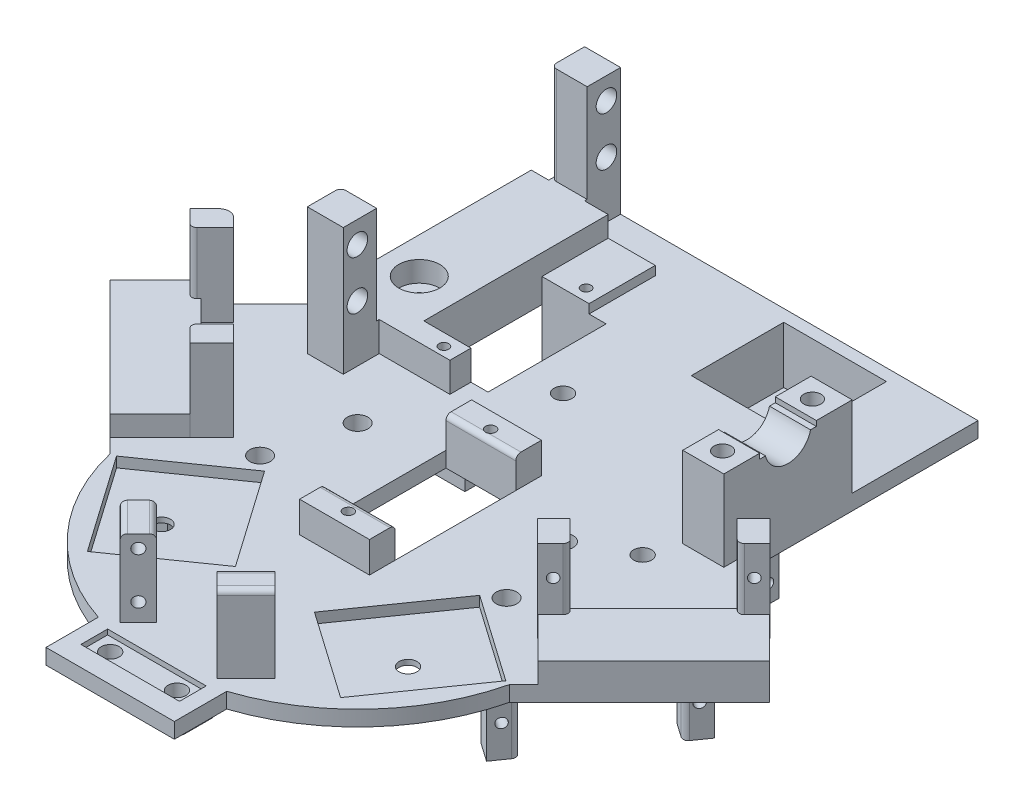
SolidWorks part; units mm, degrees
ref_plane "前视基准面" through (0, 0, 0) normal (0, 0, 1) x (1, 0, 0)
ref_plane "上视基准面" through (0, 0, 0) normal (0, 1, 0) x (1, 0, 0)
ref_plane "右视基准面" through (0, 0, 0) normal (1, 0, 0) x (0, 0, -1)
other "Configuration Table"
sketch "草图1" plane through (0, 0, 0) normal (0, 1, 0) x (1, 0, 0)
  circle A1 centre (0, 0) radius 40
  dimension "D1" = 80
extrude "凸台-拉伸1" add sketch "草图1" along normal blind 3
sketch "草图2" plane through (0, 0, 0) normal (0, -1, 0) x (-1, 0, 0)
  line L0 (-64.2199, 16.0008) -> (-38.899, -9.3201)
  line L1 (64.2199, 16.0008) -> (38.899, -9.3201)
  line L2 (-38.899, -9.3201) -> (38.899, -9.3201)
  line L3 (-64.2199, 16.0008) -> (-40, 40.2207)
  line L6 (-40, 40.2207) -> (-40, 93.8121)
  line L7 (-40, 93.8121) -> (40, 93.8121)
  line L8 (40, 93.8121) -> (40, 40.2207)
  line L9 (64.2199, 16.0008) -> (40, 40.2207)
  dimension "D1" = 77.7981
  dimension "D2" = 80
  dimension "D3" = 53.5914
  dimension "D4" = 34.2521
  dimension "D5" = 35.8091
  dimension "D6" = 53.5914
  dimension "D7" = 34.2521
  dimension "D8" = 35.8091
  dimension "D9" = 9.3201
  dimension "D10" = 56.7246
extrude "凸台-拉伸2" add sketch "草图2" against normal blind 3
sketch "草图3" plane through (0, 3, 0) normal (0, 1, 0) x (1, 0, 0)
  line L0 (-12.5, -48.1879) -> (12.5, -48.1879)
  line L1 (12.5, -48.1879) -> (12.5, -37.9967)
  line L2 (12.5, -37.9967) -> (-12.5, -37.9967)
  line L3 (-12.5, -37.9967) -> (-12.5, -48.1879)
  dimension "D1" = 37.9967
  dimension "D2" = 10.1912
  dimension "D3" = 12.5
  dimension "D4" = 12.5
extrude "凸台-拉伸3" add sketch "草图3" against normal blind 3
sketch "草图6" plane through (0, 3, 0) normal (0, 1, 0) x (1, 0, 0)
  line L3 (0, 0) -> (31.2783, -18.5118) construction
  line L5 (20.9467, 2.8224) -> (37.9031, -9.0506)
  line L6 (0, 0) -> (37.9031, -9.0506) construction
  line L7 (0, 0) -> (0, -48.1879) construction
  line L8 (37.9031, -9.0506) -> (24.6535, -27.973)
  line L9 (24.6535, -27.973) -> (7.697, -16.1)
  line L10 (7.697, -16.1) -> (20.9467, 2.8224)
  line L11 (-12.5, -48.1879) -> (12.5, -48.1879) construction
  dimension "D1" = 15.5396
  dimension "D2" = 20.7
  dimension "D3" = 23.1
  dimension "D4" = 8.7735
  dimension "D5" = 76.57
extrude "切除-拉伸2" cut sketch "草图6" against normal blind 2
mirror "镜向3" about plane through (0, 0, 0) normal (1, 0, 0) of "切除-拉伸2"
sketch "草图7" plane through (0, 1, 0) normal (0, 1, 0) x (1, 0, 0)
  circle A0 centre (-24, -14.1879) radius 1.75
  circle A1 centre (24, -14.1879) radius 1.75
  dimension "D1" = 24
  dimension "D2" = 3.5
  dimension "D4" = 3.5
  dimension "D3" = 24
  dimension "D5" = 14.1879
  dimension "D6" = 14.1879
extrude "切除-拉伸3" cut sketch "草图7" against normal blind 2
sketch "草图8" plane through (0, 3, 0) normal (0, 1, 0) x (1, 0, 0)
  line L0 (-9.6, -39.0879) -> (9.6, -39.0879)
  line L1 (9.6, -39.0879) -> (9.6, -44.2879)
  line L2 (9.6, -44.2879) -> (-9.6, -44.2879)
  line L3 (-9.6, -44.2879) -> (-9.6, -39.0879)
  dimension "D1" = 39.0879
  dimension "D2" = 5.2
  dimension "D3" = 9.6
  dimension "D4" = 9.6
extrude "切除-拉伸4" cut sketch "草图8" against normal blind 1
sketch "草图9" plane through (0, 2, 0) normal (0, 1, 0) x (1, 0, 0)
  circle A0 centre (-6.5, -41.6879) radius 1.75
  circle A1 centre (6.5, -41.6879) radius 1.75
  dimension "D1" = 3.5
  dimension "D2" = 3.5
  dimension "D3" = 6.5
  dimension "D4" = 6.5
  dimension "D5" = 41.6879
  dimension "D6" = 41.6879
extrude "切除-拉伸5" cut sketch "草图9" against normal blind 11
sketch "草图10" plane through (0, 3, 0) normal (0, 1, 0) x (1, 0, 0)
  line L13 (-14.3884, -30.4342) -> (-12.2671, -28.3129)
  line L15 (-8.7316, -36.0911) -> (-6.6103, -33.9698)
  line L18 (12.2671, -28.3129) -> (14.3884, -30.4342)
  line L21 (8.7316, -36.0911) -> (6.6103, -33.9698)
  line L22 (-6.6103, -33.9698) -> (-5.9032, -33.2627)
  line L23 (-12.2671, -28.3129) -> (-11.56, -27.6058)
  line L24 (-11.56, -27.6058) -> (-5.9032, -33.2627)
  line L25 (-8.7316, -36.0911) -> (-9.4387, -36.7982)
  line L26 (-9.4387, -36.7982) -> (-15.0955, -31.1414)
  line L27 (-15.0955, -31.1414) -> (-14.3884, -30.4342)
  line L28 (6.6103, -33.9698) -> (5.9032, -33.2627)
  line L29 (5.9032, -33.2627) -> (11.56, -27.6058)
  line L30 (11.56, -27.6058) -> (12.2671, -28.3129)
  line L31 (14.3884, -30.4342) -> (15.0955, -31.1414)
  line L32 (15.0955, -31.1414) -> (9.4387, -36.7982)
  line L33 (9.4387, -36.7982) -> (8.7316, -36.0911)
  dimension "D1" = 1
  dimension "D2" = 1
  dimension "D3" = 8
  dimension "D6" = 3
  dimension "D7" = 1
  dimension "D8" = 1
  dimension "D9" = 1
extrude "凸台-拉伸5" add sketch "草图10" along normal blind 15
fillet "圆角1" radius 1 4 edges at (8.7316, 18, 30.4342) (12.2671, 18, 33.9698) (-8.7316, 18, 30.4342) (-12.2671, 18, 33.9698)
sketch "草图12" plane through (8.0229, 0, 8.0229) normal (0.7071, 0, 0.7071) x (0.7071, 0, -0.7071)
  line L0 (-31.6944, 3) -> (-31.6944, 6.5) construction
  line L2 (-31.6944, 6.5) -> (-30.1944, 6.5) construction
  line L3 (-30.1944, 6.5) -> (-30.1944, 15.5) construction
  circle A0 centre (-30.1944, 15.5) radius 1.05
  circle A1 centre (-30.1944, 6.5) radius 1.05
  dimension "D4" = 2.1
  dimension "D5" = 2.1
  dimension "D1" = 3.5
  dimension "D2" = 1.5
  dimension "D3" = 9
extrude "切除-拉伸6" cut sketch "草图12" along normal blind 14
mirror "镜向1" about plane through (0, 0, 0) normal (1, 0, 0) of "切除-拉伸6"
sketch "草图13" plane through (0, 3, 0) normal (0, 1, 0) x (1, 0, 0)
  line L0 (32, 56.3121) -> (40, 56.3121)
  line L3 (40, 56.3121) -> (40, 31.3121)
  line L4 (40, 31.3121) -> (32, 31.3121)
  line L5 (32, 31.3121) -> (32, 56.3121)
  dimension "D1" = 25
  dimension "D2" = 8
  dimension "D3" = 32
  dimension "D4" = 56.3121
extrude "凸台-拉伸6" add sketch "草图13" along normal blind 15.75 contours L0 L3 L4 L5
sketch "草图14" plane through (40, 0, 0) normal (1, 0, 0) x (0, 0, -1)
  line L0 (56.3121, 18.75) -> (31.3121, 18.75) construction
  circle A0 centre (43.8121, 18.75) radius 4.5
  dimension "D1" = 9
extrude "切除-拉伸7" cut sketch "草图14" against normal blind 15.75
sketch "草图15" plane through (40, 0, 0) normal (1, 0, 0) x (0, 0, -1)
  line L1 (38.2871, 19.75) -> (49.3371, 19.75)
  line L2 (38.2871, 19.75) -> (38.2871, 17.75)
  line L3 (38.2871, 17.75) -> (49.3371, 17.75)
  line L4 (49.3371, 19.75) -> (49.3371, 17.75)
  line L5 (38.2871, 19.75) -> (49.3371, 17.75) construction
  line L6 (38.2871, 17.75) -> (49.3371, 19.75) construction
  point P0 (43.8121, 18.75)
  dimension "D1" = 2
  dimension "D2" = 11.05
extrude "切除-拉伸8" cut sketch "草图15" against normal blind 15.75
sketch "草图16" plane through (0, 18.75, 0) normal (0, 1, 0) x (1, 0, 0)
  circle A0 centre (36, 35.0621) radius 1.675
  circle A1 centre (36, 52.5621) radius 1.675
  dimension "D1" = 3.35
  dimension "D2" = 3.35
  dimension "D3" = 17.5
  dimension "D4" = 35.0621
  dimension "D5" = 36
  dimension "D6" = 36
extrude "切除-拉伸9" cut sketch "草图16" against normal blind 55.75
sketch "草图17" plane through (0, 3, 0) normal (0, 1, 0) x (1, 0, 0)
  line L0 (-15.8477, 73.8121) -> (-40, 73.8121)
  line L3 (-40, 73.8121) -> (-40, 33.8121)
  line L5 (-40, 33.8121) -> (-15.8477, 33.8121)
  line L6 (-15.8477, 33.8121) -> (-15.8477, 73.8121)
  dimension "D1" = 24.1523
  dimension "D2" = 33.8121
  dimension "D3" = 40
  dimension "D4" = 40
extrude "凸台-拉伸7" add sketch "草图17" along normal blind 6.75
sketch "草图18" plane through (0, 3, 0) normal (0, 1, 0) x (1, 0, 0)
  line L0 (-36.61, 73.8121) -> (-36.61, 80.8121)
  line L3 (-36.61, 80.8121) -> (-29.61, 80.8121)
  line L4 (-29.61, 80.8121) -> (-29.61, 73.8121)
  line L5 (-29.61, 73.8121) -> (-36.61, 73.8121)
  line L6 (-36.61, 33.8121) -> (-36.61, 26.8121)
  line L8 (-36.61, 26.8121) -> (-29.61, 26.8121)
  line L9 (-29.61, 26.8121) -> (-29.61, 33.8121)
  line L10 (-29.61, 33.8121) -> (-36.61, 33.8121)
  dimension "D1" = 7
  dimension "D2" = 7
  dimension "D3" = 7
  dimension "D4" = 7
  dimension "D5" = 36.61
  dimension "D6" = 33.8121
  dimension "D7" = 73.8121
  dimension "D8" = 29.61
extrude "凸台-拉伸8" add sketch "草图18" along normal blind 24.75
sketch "草图19" plane through (-36.61, 0, 0) normal (-1, 0, 0) x (0, 0, 1)
  circle A0 centre (-29.5621, 23.5) radius 2
  circle A1 centre (-29.5621, 14) radius 2
  circle A2 centre (-78.0621, 23.5) radius 2
  circle A3 centre (-78.0621, 14) radius 2
  dimension "D1" = 4
  dimension "D2" = 4
  dimension "D3" = 4
  dimension "D4" = 4
  dimension "D5" = 29.5621
  dimension "D6" = 14
  dimension "D7" = 48.5
  dimension "D8" = 48.5
  dimension "D9" = 9.5
extrude "切除-拉伸10" cut sketch "草图19" against normal blind 24.75
sketch "草图20" plane through (0, 27.75, 0) normal (0, 1, 0) x (1, 0, 0)
  line L0 (-36.61, 73.8121) -> (-29.61, 73.8121)
  line L1 (-29.61, 73.8121) -> (-29.61, 74.3121)
  line L2 (-29.61, 74.3121) -> (-36.61, 74.3121)
  line L3 (-36.61, 80.8121) -> (-36.61, 73.8121) construction
  line L4 (-36.61, 74.3121) -> (-36.61, 73.8121)
  line L5 (-29.61, 33.8121) -> (-29.61, 33.3121)
  line L6 (-29.61, 26.8121) -> (-29.61, 33.8121) construction
  line L7 (-29.61, 33.3121) -> (-36.61, 33.3121)
  line L8 (-36.61, 33.8121) -> (-36.61, 26.8121) construction
  line L9 (-36.61, 33.3121) -> (-36.61, 33.8121)
  line L10 (-36.61, 33.8121) -> (-29.61, 33.8121)
  dimension "D1" = 0.5
  dimension "D2" = 0.5
extrude "切除-拉伸11" cut sketch "草图20" against normal blind 19
fillet "圆角2" radius 1 2 edges at (-36.61, 18.25, -33.3121) (-36.61, 18.25, -74.3121)
sketch "草图21" plane through (0, 0, 0) normal (0, -1, 0) x (1, 0, 0)
  line L0 (-34.2042, 9.1029) -> (-30.518, 6.5218)
  line L1 (-30.518, 6.5218) -> (-33.0991, 2.8356)
  line L2 (-33.0991, 2.8356) -> (-36.7853, 5.4167)
  line L3 (-36.7853, 5.4167) -> (-34.2042, 9.1029)
  line L4 (-52.5013, -17.0281) -> (-48.8151, -19.6092)
  line L5 (-48.8151, -19.6092) -> (-46.234, -15.923)
  line L6 (-46.234, -15.923) -> (-49.9202, -13.3419)
  line L7 (-49.9202, -13.3419) -> (-52.5013, -17.0281)
  dimension "D1" = 4.5
  dimension "D2" = 4.5
  dimension "D3" = 4.5
  dimension "D4" = 4.5
  dimension "D5" = 33.0991
  dimension "D6" = 2.8356
  dimension "D7" = 34.2042
  dimension "D8" = 46.234
  dimension "D9" = 15.923
extrude "凸台-拉伸9" add sketch "草图21" along normal blind 12.4
sketch "草图22" plane through (-27.2283, 0, 19.0655) normal (-0.8192, 0, 0.5736) x (0.5736, 0, 0.8192)
  line L0 (-12.1621, 0) -> (-12.1621, -6.2) construction
  line L1 (-12.1621, -12.4) -> (-12.1621, 0) construction
  line L2 (-12.1621, -6.2) -> (-14.2621, -6.2) construction
  line L3 (-44.0621, 0) -> (-44.0621, -6.2) construction
  line L4 (-44.0621, -12.4) -> (-44.0621, 0) construction
  line L5 (-44.0621, -6.2) -> (-41.9621, -6.2) construction
  circle A0 centre (-41.9621, -6.2) radius 0.95
  circle A1 centre (-14.2621, -6.2) radius 0.95
  dimension "D3" = 1.9
  dimension "D4" = 1.9
  dimension "D1" = 2.1
  dimension "D2" = 2.1
extrude "切除-拉伸12" cut sketch "草图22" against normal blind 12.4
fillet "圆角3" radius 1 2 edges at (-36.7853, -6.2, 5.4167) (-49.9202, -6.2, -13.3419)
mirror "镜向2" about plane through (0, 0, 0) normal (1, 0, 0) of "圆角3", "凸台-拉伸9", "切除-拉伸12"
sketch "草图23" plane through (0, 0, 0) normal (0, -1, 0) x (1, 0, 0)
  line L0 (12.56, -24.6821) -> (17.06, -24.6821)
  line L1 (17.06, -24.6821) -> (17.06, -29.1821)
  line L2 (17.06, -29.1821) -> (12.56, -29.1821)
  line L3 (12.56, -29.1821) -> (12.56, -24.6821)
  line L4 (17.06, -52.0821) -> (17.06, -56.5821)
  line L5 (17.06, -56.5821) -> (12.56, -56.5821)
  line L6 (12.56, -56.5821) -> (12.56, -52.0821)
  line L7 (12.56, -52.0821) -> (17.06, -52.0821)
  line L8 (17.06, -61.5821) -> (17.06, -66.0821)
  line L9 (17.06, -66.0821) -> (12.56, -66.0821)
  line L10 (12.56, -66.0821) -> (12.56, -61.5821)
  line L11 (12.56, -61.5821) -> (17.06, -61.5821)
  line L12 (17.06, -88.9821) -> (17.06, -93.4821)
  line L13 (17.06, -93.4821) -> (12.56, -93.4821)
  line L14 (12.56, -93.4821) -> (12.56, -88.9821)
  line L15 (12.56, -88.9821) -> (17.06, -88.9821)
  point P30 (14.81, -88.9821)
  dimension "D1" = 4.5
  dimension "D2" = 4.5
  dimension "D3" = 4.5
  dimension "D4" = 4.5
  dimension "D5" = 4.5
  dimension "D6" = 4.5
  dimension "D7" = 24.6821
  dimension "D8" = 12.56
  dimension "D9" = 12.56
  dimension "D10" = 52.0821
  dimension "D11" = 17.06
  dimension "D12" = 61.5821
  dimension "D13" = 4.5
  dimension "D14" = 4.5
  dimension "D15" = 12.56
  dimension "D16" = 88.9821
extrude "凸台-拉伸10" add sketch "草图23" along normal blind 12.4
sketch "草图24" plane through (12.56, 0, 0) normal (-1, 0, 0) x (0, 0, 1)
  line L0 (-93.4821, 0) -> (-93.4821, -6.2) construction
  line L1 (-93.4821, -12.4) -> (-93.4821, 0) construction
  line L2 (-93.4821, -6.2) -> (-91.3821, -6.2) construction
  line L3 (-61.5821, 0) -> (-61.5821, -6.2) construction
  line L4 (-61.5821, -12.4) -> (-61.5821, 0) construction
  line L5 (-61.5821, -6.2) -> (-63.6821, -6.2) construction
  line L6 (-56.5821, 0) -> (-56.5821, -6.2) construction
  line L7 (-56.5821, -12.4) -> (-56.5821, 0) construction
  line L8 (-56.5821, -6.2) -> (-54.4821, -6.2) construction
  line L9 (-24.6821, 0) -> (-24.6821, -6.2) construction
  line L10 (-24.6821, -12.4) -> (-24.6821, 0) construction
  line L11 (-24.6821, -6.2) -> (-26.7821, -6.2) construction
  circle A0 centre (-91.3821, -6.2) radius 0.95
  circle A1 centre (-63.6821, -6.2) radius 0.95
  circle A2 centre (-54.4821, -6.2) radius 0.95
  circle A3 centre (-26.7821, -6.2) radius 0.95
  dimension "D5" = 1.9
  dimension "D6" = 1.9
  dimension "D7" = 1.9
  dimension "D8" = 1.9
  dimension "D1" = 2.1
  dimension "D2" = 2.1
  dimension "D3" = 2.1
  dimension "D4" = 2.1
extrude "切除-拉伸13" cut sketch "草图24" against normal blind 12.4
sketch "草图33" plane through (0, 0, 0) normal (0, -1, 0) x (1, 0, 0)
  line L0 (-5.44, 11.1879) -> (-5.44, 4.1879)
  line L1 (-5.44, 4.1879) -> (-2.44, 4.1879)
  line L2 (-2.44, 4.1879) -> (-2.44, 11.1879)
  line L3 (-2.44, 11.1879) -> (-5.44, 11.1879)
  point P9 (-3.94, 4.1879)
  dimension "D1" = 4.1879
  dimension "D2" = 2.44
  dimension "D3" = 7
  dimension "D4" = 3.94
extrude "凸台-拉伸14" add sketch "草图33" along normal blind 12
sketch "草图34" plane through (-2.44, 0, 0) normal (1, 0, 0) x (0, 0, -1)
  line L0 (-7.6879, 0) -> (-7.6879, -7.1) construction
  line L1 (-4.1879, 0) -> (-11.1879, 0) construction
  circle A0 centre (-7.6879, -7.1) radius 1.5
  dimension "D2" = 3
  dimension "D1" = 7.1
extrude "切除-拉伸18" cut sketch "草图34" against normal blind 12
fillet "圆角4" radius 1 2 edges at (-3.94, -12, 4.1879) (-3.94, -12, 11.1879)
sketch "草图36" plane through (0, 3, 0) normal (0, 1, 0) x (1, 0, 0)
  line L0 (7.9297, 89.0668) -> (7.9297, 88.9712) construction
  line L7 (7.9297, 89.0668) -> (8.9297, 89.0668)
  line L12 (7.9591, 66.1712) -> (7.9591, 66.0712) construction
  line L13 (7.9591, 66.0712) -> (8.9591, 66.0712)
  point P8 (7.9591, 77.5712)
  point P11 (7.9591, 77.5712)
  dimension "D1" = 22.9956
  dimension "D2" = 1
  dimension "D3" = 89.0668
  dimension "D5" = 0.1
  dimension "D6" = 1
sketch "草图45" plane through (0, 0, 0) normal (0, -1, 0) x (1, 0, 0)
  line L14 (12.56, -56.5821) -> (9.56, -56.5821) construction
  line L15 (9.56, -56.5821) -> (9.56, -56.6321) construction
  line L16 (9.56, -56.6321) -> (3.56, -56.6321)
  line L17 (3.56, -56.6321) -> (3.56, -52.1321)
  line L18 (3.56, -52.1321) -> (9.56, -52.1321)
  line L19 (9.56, -52.1321) -> (9.56, -56.6321)
  line L20 (12.56, -24.6821) -> (9.56, -24.6821) construction
  line L21 (9.56, -24.6821) -> (9.56, -24.6321) construction
  line L22 (9.56, -24.6321) -> (9.56, -29.1321)
  line L23 (9.56, -29.1321) -> (3.56, -29.1321)
  line L24 (3.56, -29.1321) -> (3.56, -24.6321)
  line L25 (3.56, -24.6321) -> (9.56, -24.6321)
  dimension "D13" = 0.05
  dimension "D14" = 6
  dimension "D15" = 4.5
  dimension "D16" = 3
  dimension "D17" = 0.05
  dimension "D18" = 4.5
  dimension "D19" = 6
  dimension "D20" = 4.5
extrude "凸台-拉伸21" add sketch "草图45" along normal blind 12.4
extrude "切除-拉伸22" cut sketch "草图24<2>" along normal blind 12.4
sketch "草图24<2>" plane through (12.56, 0, 0) normal (-1, 0, 0) x (0, 0, 1) same geometry as "草图24"
sketch "草图47" plane through (0, -12.4, 0) normal (0, -1, 0) x (1, 0, 0)
  line L0 (12.56, -24.6821) -> (12.56, -29.1821)
  line L1 (12.56, -29.1821) -> (17.06, -29.1821)
  line L2 (17.06, -29.1821) -> (17.06, -24.6821)
  line L3 (17.06, -24.6821) -> (12.56, -24.6821)
  line L4 (12.56, -52.0821) -> (12.56, -56.5821)
  line L5 (12.56, -56.5821) -> (17.06, -56.5821)
  line L6 (17.06, -56.5821) -> (17.06, -52.0821)
  line L7 (17.06, -52.0821) -> (12.56, -52.0821)
  line L8 (12.56, -61.5821) -> (12.56, -66.0821)
  line L9 (12.56, -66.0821) -> (17.06, -66.0821)
  line L10 (17.06, -66.0821) -> (17.06, -61.5821)
  line L11 (17.06, -61.5821) -> (12.56, -61.5821)
  line L12 (12.56, -88.9821) -> (12.56, -93.4821)
  line L13 (12.56, -93.4821) -> (17.06, -93.4821)
  line L14 (17.06, -93.4821) -> (17.06, -88.9821)
  line L15 (17.06, -88.9821) -> (12.56, -88.9821)
extrude "切除-拉伸23" cut sketch "草图47" against normal blind 12.4
fillet "圆角6" radius 1 2 edges at (9.56, -6.2, -52.1321) (9.56, -6.2, -29.1321)
sketch "草图50" plane through (0, 3, 0) normal (0, 1, 0) x (1, 0, 0)
  line L0 (-64.2199, 16.0008) -> (-55.3811, 24.8396)
  line L3 (-55.3811, 24.8396) -> (-32.8244, 2.2829)
  line L4 (-32.8244, 2.2829) -> (-41.6632, -6.556)
  line L7 (-41.6632, -6.556) -> (-64.2199, 16.0008)
  line L8 (64.2199, 16.0008) -> (55.3811, 24.8396)
  line L11 (55.3811, 24.8396) -> (32.8244, 2.2829)
  line L12 (32.8244, 2.2829) -> (41.6632, -6.556)
  line L15 (41.6632, -6.556) -> (64.2199, 16.0008)
  dimension "D1" = 12.5
  dimension "D2" = 31.9
  dimension "D3" = 32.8244
  dimension "D4" = 2.2829
  dimension "D5" = 55.3811
  dimension "D6" = 32.8244
  dimension "D7" = 2.2829
extrude "凸台-拉伸22" add sketch "草图50" along normal blind 4
sketch "草图51" plane through (0, 7, 0) normal (0, 1, 0) x (1, 0, 0)
  line L0 (58.5631, 21.6576) -> (56.4417, 23.7789) construction
  line L3 (56.4417, 23.7789) -> (56.4771, 23.8143) construction
  line L4 (56.4771, 23.8143) -> (52.2345, 28.0569)
  line L5 (52.2345, 28.0569) -> (49.0525, 24.8749)
  line L6 (49.0525, 24.8749) -> (53.2951, 20.6323)
  line L8 (36.0064, -0.8991) -> (33.885, 1.2222) construction
  line L11 (33.885, 1.2222) -> (33.8497, 1.1869) construction
  line L12 (33.8497, 1.1869) -> (29.607, 5.4295)
  line L13 (29.607, 5.4295) -> (32.789, 8.6115)
  line L14 (32.789, 8.6115) -> (37.0317, 4.3688)
  line L15 (37.0317, 4.3688) -> (33.8497, 1.1869)
  line L17 (-37.0317, 4.3688) -> (-33.8497, 1.1869)
  line L18 (-33.8497, 1.1869) -> (-29.607, 5.4295)
  line L19 (-29.607, 5.4295) -> (-32.789, 8.6115)
  line L20 (-32.789, 8.6115) -> (-37.0317, 4.3688)
  line L21 (-52.2345, 28.0569) -> (-49.0525, 24.8749)
  line L22 (-56.4771, 23.8143) -> (-52.2345, 28.0569)
  line L23 (-53.2951, 20.6323) -> (-56.4771, 23.8143)
  line L24 (-49.0525, 24.8749) -> (-53.2951, 20.6323)
  line L26 (53.2951, 20.6323) -> (56.4771, 23.8143)
  dimension "D1" = 3
  dimension "D2" = 0.05
  dimension "D3" = 6
  dimension "D4" = 4.5
  dimension "D5" = 6
  dimension "D6" = 3
  dimension "D7" = 0.05
  dimension "D8" = 6
  dimension "D9" = 4.5
  dimension "D10" = 6
  dimension "D11" = 6
  dimension "D12" = 4.5
  dimension "D13" = 53.2951
  dimension "D14" = 20.6323
  dimension "D15" = 90
  dimension "D16" = 90
  dimension "D17" = 90
  dimension "D18" = 24.8749
  dimension "D19" = 6
  dimension "D20" = 4.5
  dimension "D21" = 30.1008
  dimension "D22" = 29.607
  dimension "D23" = 32.789
  dimension "D24" = 29.607
  dimension "D25" = 5.4295
  dimension "D26" = 37.0317
  dimension "D27" = 49.0525
  dimension "D28" = 24.8749
  dimension "D29" = 53.2951
extrude "凸台-拉伸23" add sketch "草图51" along normal blind 12
extrude "凸台-拉伸25" add sketch "草图51<3>" against normal blind 4
sketch "草图51<3>" plane through (0, 7, 0) normal (0, 1, 0) x (1, 0, 0) same geometry as "草图51"
sketch "草图52" plane through (16.3314, 0, 16.3314) normal (0.7071, 0, 0.7071) x (0.7071, 0, -0.7071)
  circle A2 centre (54.6246, 13.2) radius 0.95
  circle A3 centre (26.9246, 13.2) radius 0.95
  dimension "D1" = 1.9
  dimension "D2" = 1.9
  dimension "D3" = 26.9246
  dimension "D4" = 13.2
  dimension "D5" = 27.7
  dimension "D6" = 13.2
extrude "切除-拉伸25" cut sketch "草图52" against normal blind 14
fillet "圆角7" radius 1 4 edges at (37.0317, 13, -4.3688) (-37.0317, 13, -4.3688) (-53.2951, 13, -20.6323) (53.2951, 13, -20.6323)
sketch "草图53" plane through (-16.3314, 0, 16.3314) normal (-0.7071, 0, 0.7071) x (0.7071, 0, 0.7071)
  circle A0 centre (-54.6246, 13.2) radius 0.95
  circle A1 centre (-26.9246, 13.2) radius 0.95
  dimension "D1" = 1.9
  dimension "D2" = 1.9
  dimension "D3" = 26.9246
  dimension "D4" = 13.2
  dimension "D5" = 54.6246
  dimension "D6" = 13.2
extrude "切除-拉伸26" cut sketch "草图53" against normal blind 14
sketch "草图65" plane through (0, 9.75, 0) normal (0, 1, 0) x (1, 0, 0)
  line L0 (-15.8477, 73.8121) -> (-15.8477, 33.8121)
  line L1 (-15.8477, 33.8121) -> (-40, 33.8121)
  line L2 (-40, 33.8121) -> (-40, 73.8121)
  line L3 (-40, 73.8121) -> (-15.8477, 73.8121)
extrude "切除-拉伸28" cut sketch "草图65" against normal blind 1
sketch "草图67" plane through (0, 2, 0) normal (0, 1, 0) x (1, 0, 0)
  line L0 (0, -39.0879) -> (0, -44.2879) construction
  line L1 (9.6, -39.0879) -> (-9.6, -39.0879) construction
  line L2 (-9.6, -44.2879) -> (9.6, -44.2879) construction
  line L4 (-10.6, -38.0879) -> (10.6, -38.0879)
  line L5 (-10.6, -38.0879) -> (-10.6, -45.2879)
  line L6 (-10.6, -45.2879) -> (10.6, -45.2879)
  line L7 (10.6, -38.0879) -> (10.6, -45.2879)
  line L8 (-10.6, -38.0879) -> (10.6, -45.2879) construction
  line L9 (-10.6, -45.2879) -> (10.6, -38.0879) construction
  circle A0 centre (-6.5, -41.6879) radius 1.75
  circle A1 centre (6.5, -41.6879) radius 1.75
  point P6 (0, -41.6879)
  dimension "D1" = 7.2
  dimension "D2" = 21.2
extrude "凸台-拉伸33" add sketch "草图67" against normal blind 2 from offset 2 offset against normal yes
fillet "圆角10" radius 1 4 edges at (-10.6, -1, 38.0879) (10.6, -1, 38.0879) (-10.6, -1, 45.2879) (10.6, -1, 45.2879)
fillet "圆角11" radius 2 1 edges at (-52.2345, 11, -28.0569)
sketch "草图70" plane through (0, 3, 0) normal (0, 1, 0) x (1, 0, 0)
  line L0 (-20, 20) -> (20, 20)
  circle A0 centre (-20, 20) radius 2
  circle A1 centre (20, 20) radius 2
  point P2 (0, 20)
  dimension "D3" = 4
  dimension "D4" = 4
  dimension "D1" = 20
  dimension "D2" = 40
extrude "切除-拉伸31" cut sketch "草图70" against normal blind 10 contours A1 | A0 region at (20, 3, -21.9434) region at (-21.9434, 3, -20)
sketch "草图71" plane through (0, 3, 0) normal (0, 1, 0) x (1, 0, 0)
  circle A0 centre (24, 5) radius 2
  circle A1 centre (-24, 5) radius 2
  dimension "D1" = 48
  dimension "D2" = 24
  dimension "D3" = 4
  dimension "D4" = 5
  dimension "D5" = 4
extrude "切除-拉伸32" cut sketch "草图71" against normal blind 10 contours A0 | A1 region at (24, 3, -5) region at (-24, 3, -5)
sketch "草图73" plane through (0, 3, 0) normal (0, 1, 0) x (1, 0, 0)
  line L1 (-6.8, 24) -> (6.8, 24)
  line L2 (-6.8, 24) -> (-6.8, 0.5)
  line L3 (-6.8, 0.5) -> (6.8, 0.5)
  line L12 (6.8, 24) -> (6.8, 0.5)
  line L13 (-6.8, 24) -> (6.8, 0.5) construction
  line L14 (-6.8, 0.5) -> (6.8, 24) construction
  point P2 (0, 12.25)
  dimension "D2" = 23.5
  dimension "D3" = 13.6
  dimension "D1" = 0.5
extrude "切除-拉伸34" cut sketch "草图73" against normal blind 10
sketch "草图74" plane through (0, 3, 0) normal (0, 1, 0) x (1, 0, 0)
  line L0 (6.8, 0.5) -> (6.8, 24) construction
  line L1 (-6.8, 24) -> (6.8, 24)
  line L2 (-6.8, 24) -> (-6.8, 29)
  line L3 (-6.8, 29) -> (6.8, 29)
  line L4 (6.8, 24) -> (6.8, 29)
  line L5 (-6.8, 0.5) -> (6.8, 0.5)
  line L6 (-6.8, 0.5) -> (-6.8, -4.5)
  line L7 (-6.8, -4.5) -> (6.8, -4.5)
  line L8 (6.8, 0.5) -> (6.8, -4.5)
  dimension "D1" = 5
  dimension "D2" = 5
extrude "凸台-拉伸34" add sketch "草图74" along normal blind 6
sketch "草图75" plane through (0, 0, 0) normal (0, -1, 0) x (1, 0, 0)
  line L4 (19.6, -24.7821) -> (19.6, -29.0393) construction
  line L5 (19.6, -52.2249) -> (19.6, -56.4821) construction
  line L8 (19.6, -24.7821) -> (25.6, -24.7821)
  line L9 (25.6, -24.7821) -> (25.6, -29.2321)
  line L10 (25.6, -29.2321) -> (19.6, -29.2321)
  line L11 (19.6, -29.2321) -> (19.6, -24.7821)
  line L12 (19.6, -56.4821) -> (25.6, -56.4821)
  line L13 (25.6, -56.4821) -> (25.6, -52.0321)
  line L14 (25.6, -52.0321) -> (19.6, -52.0321)
  line L15 (19.6, -52.0321) -> (19.6, -56.4821)
  dimension "D1" = 6
  dimension "D2" = 6
  dimension "D3" = 4.45
  dimension "D4" = 4.45
  dimension "D5" = 25.6
  dimension "D6" = 24.7821
  dimension "D7" = 52.0321
  dimension "D8" = 19.6
  dimension "D9" = 52.2249
  dimension "D10" = 29.0393
  dimension "D11" = 19.6
  dimension "D12" = 19.6
extrude "凸台-拉伸35" add sketch "草图75" along normal blind 22
sketch "草图76" plane through (19.6, 0, 0) normal (-1, 0, 0) x (0, 0, 1)
  circle A0 centre (-54.4821, -18.6) radius 0.95
  circle A1 centre (-26.7821, -18.6) radius 0.95
  dimension "D1" = 1.9
  dimension "D2" = 1.9
  dimension "D3" = 18.6
  dimension "D4" = 26.7821
  dimension "D5" = 18.6
  dimension "D6" = 54.4821
extrude "切除-拉伸35" cut sketch "草图76" against normal blind 10
sketch "草图78" plane through (0, 3, 0) normal (0, 1, 0) x (1, 0, 0)
  line L0 (-40, 73.8121) -> (-40, 93.8121) construction
  line L1 (-40, 80.8121) -> (40, 80.8121)
  line L2 (-40, 80.8121) -> (-40, 93.8121)
  line L3 (-40, 93.8121) -> (40, 93.8121)
  line L4 (40, 80.8121) -> (40, 93.8121)
  line L5 (-29.61, 80.8121) -> (-36.61, 80.8121) construction
extrude "切除-拉伸36" cut sketch "草图78" against normal through all
sketch "草图79" plane through (0, 0, 0) normal (0, -1, 0) x (1, 0, 0)
  line L0 (19.6, -56.4821) -> (25.6, -56.4821) construction
  line L1 (2, -59.4821) -> (27, -59.4821)
  line L2 (2, -59.4821) -> (2, -79.4821)
  line L3 (2, -79.4821) -> (27, -79.4821)
  line L4 (27, -59.4821) -> (27, -79.4821)
  line L5 (40, -80.8121) -> (40, -40.2207) construction
  dimension "D1" = 20
  dimension "D2" = 25
  dimension "D3" = 3
  dimension "D4" = 13
extrude "凸台-拉伸36" add sketch "草图79" along normal blind 12.3
sketch "草图80" plane through (0, -12.3, 0) normal (0, -1, 0) x (1, 0, 0)
  line L0 (27, -59.4821) -> (2, -59.4821) construction
  line L1 (2.75, -78.2321) -> (26.25, -78.2321)
  line L2 (2.75, -78.2321) -> (2.75, -60.7321)
  line L3 (2.75, -60.7321) -> (26.25, -60.7321)
  line L4 (26.25, -78.2321) -> (26.25, -60.7321)
  line L5 (2.75, -78.2321) -> (26.25, -60.7321) construction
  line L6 (2.75, -60.7321) -> (26.25, -78.2321) construction
  line L8 (27, -79.4821) -> (27, -59.4821) construction
  point P0 (14.5, -69.4821)
  point P8 (14.5, -59.4821)
  point P14 (27, -69.4821)
  dimension "D1" = 23.5
  dimension "D2" = 17.5
extrude "切除-拉伸37" cut sketch "草图80" against normal blind 2
sketch "草图81" plane through (0, 3, 0) normal (0, 1, 0) x (1, 0, 0)
  line L1 (4.5, 60.4821) -> (24.5, 60.4821)
  line L2 (4.5, 60.4821) -> (4.5, 78.4821)
  line L3 (4.5, 78.4821) -> (24.5, 78.4821)
  line L4 (24.5, 60.4821) -> (24.5, 78.4821)
  line L5 (27, 59.4821) -> (2, 59.4821) construction
  line L6 (27, 79.4821) -> (27, 59.4821) construction
  point P6 (14.5, 59.4821)
  point P7 (14.5, 60.4821)
  point P10 (27, 69.4821)
  point P11 (24.5, 69.4821)
  dimension "D1" = 20
  dimension "D2" = 18
extrude "切除-拉伸38" cut sketch "草图81" against normal blind 11
sketch "草图82" plane through (0, -10.3, 0) normal (0, -1, 0) x (-1, 0, 0)
  line L0 (-27, 59.4821) -> (-2, 59.4821) construction
  line L1 (-10.5, 75.4821) -> (-18.5, 75.4821) construction
  line L2 (-10.5, 75.4821) -> (-10.5, 63.4821) construction
  line L3 (-10.5, 63.4821) -> (-18.5, 63.4821) construction
  line L4 (-18.5, 75.4821) -> (-18.5, 63.4821) construction
  line L5 (-10.5, 75.4821) -> (-18.5, 63.4821) construction
  line L6 (-10.5, 63.4821) -> (-18.5, 75.4821) construction
  line L7 (-27, 79.4821) -> (-27, 59.4821) construction
  circle A0 centre (-10.5, 63.4821) radius 1.25
  circle A1 centre (-18.5, 63.4821) radius 1.25
  circle A2 centre (-10.5, 75.4821) radius 1.25
  circle A3 centre (-18.5, 75.4821) radius 1.25
  point P0 (-14.5, 69.4821)
  point P8 (-14.5, 59.4821)
  point P11 (-27, 69.4821)
  dimension "D3" = 2.5
  dimension "D1" = 12
  dimension "D2" = 8
extrude "切除-拉伸40" cut sketch "草图82" against normal blind 12
sketch "草图83" plane through (0, 3, 0) normal (0, 1, 0) x (1, 0, 0)
  line L1 (-12.5166, 60.9121) -> (-25.0166, 60.9121)
  line L2 (-12.5166, 60.9121) -> (-12.5166, 37.9121)
  line L3 (-12.5166, 37.9121) -> (-25.0166, 37.9121)
  line L4 (-25.0166, 60.9121) -> (-25.0166, 37.9121)
  dimension "D1" = 23
  dimension "D2" = 12.5
  dimension "D3" = 25.0166
  dimension "D4" = 60.9121
extrude "切除-拉伸41" cut sketch "草图83" against normal blind 12 and the other way blind 12
sketch "草图84" plane through (0, 0, 0) normal (0, -1, 0) x (1, 0, 0)
  line L1 (-25.0166, -37.9121) -> (-12.5166, -37.9121)
  line L2 (-25.0166, -37.9121) -> (-25.0166, -33.4121)
  line L3 (-25.0166, -33.4121) -> (-12.5166, -33.4121)
  line L4 (-12.5166, -37.9121) -> (-12.5166, -33.4121)
  line L5 (-25.0166, -60.9121) -> (-12.5166, -60.9121)
  line L6 (-25.0166, -60.9121) -> (-25.0166, -65.4121)
  line L7 (-25.0166, -65.4121) -> (-12.5166, -65.4121)
  line L8 (-12.5166, -60.9121) -> (-12.5166, -65.4121)
  dimension "D1" = 4.5
  dimension "D2" = 4.5
  dimension "D3" = 33.4121
  dimension "D4" = 12.5166
  dimension "D5" = 25.0166
  dimension "D6" = 12.5166
  dimension "D7" = 60.9121
  dimension "D8" = 12.5
extrude "凸台-拉伸37" add sketch "草图84" along normal blind 11.55
sketch "草图85" plane through (0, -11.55, 0) normal (0, -1, 0) x (1, 0, 0)
  circle A0 centre (-18.7666, -63.2621) radius 0.95
  circle A1 centre (-18.7666, -35.5621) radius 0.95
  dimension "D1" = 1.9
  dimension "D2" = 1.9
  dimension "D3" = 35.5621
  dimension "D4" = 18.7666
  dimension "D5" = 27.7
extrude "切除-拉伸42" cut sketch "草图85" against normal through all
sketch "草图86" plane through (0, 8.75, 0) normal (0, 1, 0) x (1, 0, 0)
  line L0 (-15.8477, 73.8121) -> (-29.61, 73.8121) construction
  line L1 (-15.8477, 60.9121) -> (-25.0166, 60.9121)
  line L2 (-15.8477, 60.9121) -> (-15.8477, 73.8121)
  line L3 (-15.8477, 73.8121) -> (-25.0166, 73.8121)
  line L4 (-25.0166, 60.9121) -> (-25.0166, 73.8121)
  line L5 (-25.0166, 37.9121) -> (-25.0166, 60.9121) construction
  line L6 (-25.0166, 60.9121) -> (-15.8477, 60.9121) construction
extrude "切除-拉伸43" cut sketch "草图86" against normal blind 4
fillet "圆角13" radius 1 2 edges at (0, 9, -0.5) (0, 9, -24)
fillet "圆角14" radius 1 2 edges at (19.6, -11, -29.2321) (19.6, -11, -52.0321)
sketch "草图94" plane through (0, 8.75, 0) normal (0, 1, 0) x (1, 0, 0)
  circle A0 centre (-33, 45) radius 4
  dimension "D1" = 8
  dimension "D2" = 33
  dimension "D3" = 45
extrude "切除-拉伸45" cut sketch "草图94" against normal blind 4
sketch "草图95" plane through (0, 4.75, 0) normal (0, 1, 0) x (1, 0, 0)
  circle A0 centre (-33, 45) radius 1.75
  dimension "D1" = 3.5
extrude "切除-拉伸46" cut sketch "草图95" against normal blind 8
sketch "草图96" plane through (0, 3, 0) normal (0, 1, 0) x (1, 0, 0)
  circle A0 centre (30, 58) radius 1.75
  circle A1 centre (30, 25.5) radius 1.75
  circle A2 centre (-33, 45) radius 4 construction
  dimension "D1" = 3.5
  dimension "D4" = 19.5
  dimension "D5" = 3.5
  dimension "D2" = 30
  dimension "D3" = 58
extrude "切除-拉伸47" cut sketch "草图96" against normal blind 8
sketch "草图97" plane through (0, 0, 0) normal (0, -1, 0) x (1, 0, 0)
  circle A0 centre (-5, -45) radius 1.75
  dimension "D1" = 3.5
  dimension "D2" = 45
  dimension "D3" = 5
extrude "切除-拉伸48" cut sketch "草图97" against normal blind 8
sketch "草图98" plane through (0, 9, 0) normal (0, 1, 0) x (1, 0, 0)
  line L0 (-6.8, 0.5) -> (6.8, 0.5) construction
  circle A0 centre (0, -1.8) radius 1
  circle A1 centre (0, 25.9) radius 1
  dimension "D1" = 2.3
  dimension "D2" = 27.7
  dimension "D3" = 2
  dimension "D4" = 2
extrude "切除-拉伸49" cut sketch "草图98" against normal blind 10
